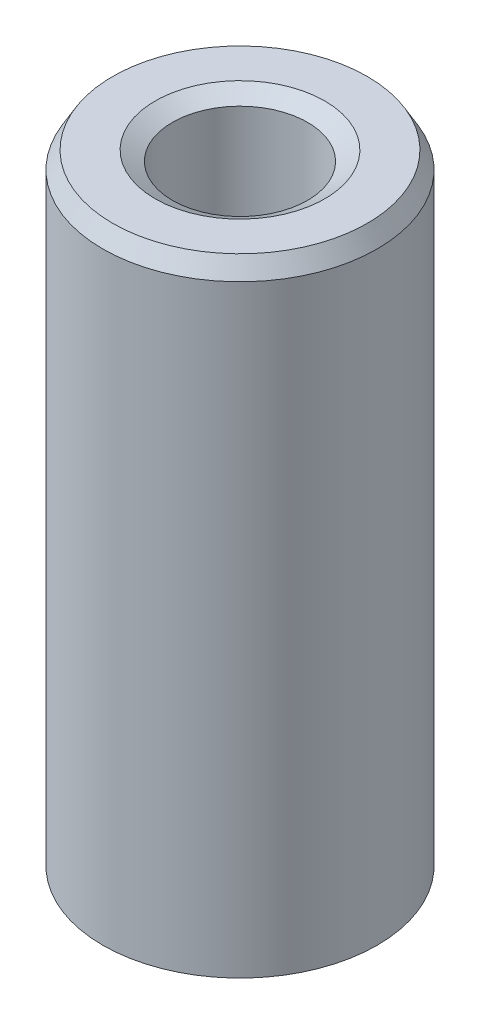
SolidWorks part; units mm, degrees
ref_plane "Front Plane" through (0, 0, 0) normal (0, 0, 1) x (1, 0, 0)
ref_plane "Top Plane" through (0, 0, 0) normal (0, 1, 0) x (1, 0, 0)
ref_plane "Right Plane" through (0, 0, 0) normal (1, 0, 0) x (0, 0, -1)
sketch "Sketch1" plane through (0, 0, 0) normal (0, 1, 0) x (1, 0, 0)
  circle A0 centre (0, 0) radius 22.5
  dimension "SLEEVE_OD" = 45
extrude "Boss-Extrude1" add sketch "Sketch1" along normal blind 103.3414
sketch "Sketch2" plane through (0, 0, 0) normal (0, 1, 0) x (1, 0, 0)
  circle A0 centre (0, 0) radius 11.0872
  dimension "BORE_D" = 22.1744
extrude "Cut-Extrude1" cut sketch "Sketch2" along normal through all
chamfer "Chamfer1" distance 2.8209 angle 30 4 edges at (0, 103.3414, 11.0872) (0, 0, 11.0872) (0, 0, 22.5) (0, 103.3414, 22.5) first distance on face at (0, 103.3414, 11.0872) first distance on face at (0, 0, 11.0872) first distance on face at (0, 103.3414, 22.5)
